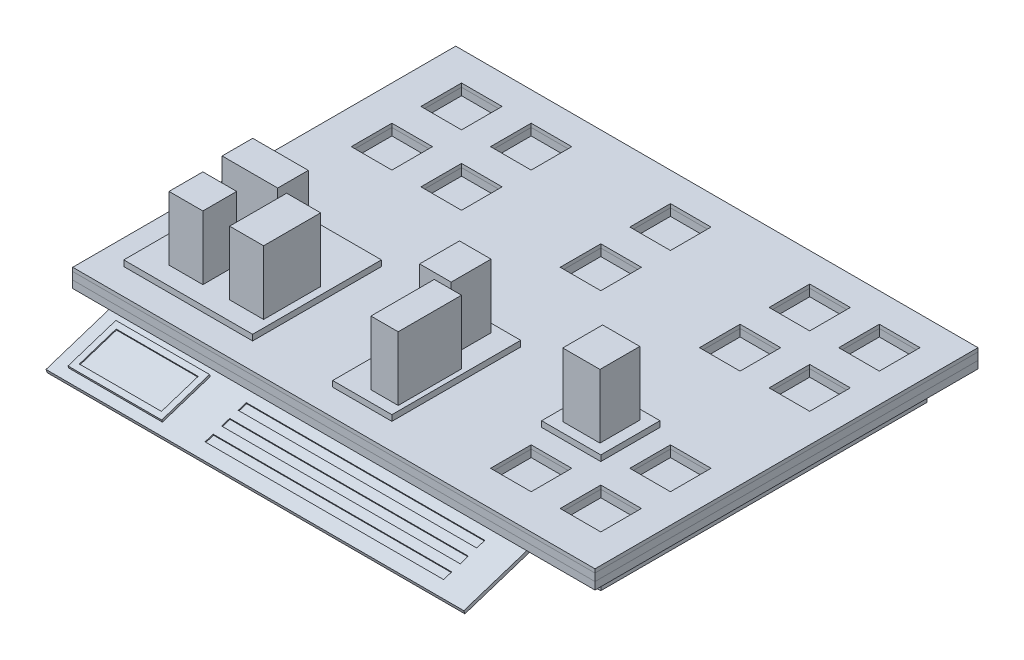
SolidWorks part; units mm, degrees
ref_plane "Front Plane" through (0, 0, 0) normal (0, 0, 1) x (1, 0, 0)
ref_plane "Top Plane" through (0, 0, 0) normal (0, 1, 0) x (1, 0, 0)
ref_plane "Right Plane" through (0, 0, 0) normal (1, 0, 0) x (0, 0, -1)
sketch "Sketch2" plane through (0, 0, 0) normal (0, 1, 0) x (1, 0, 0)
  line L0 (60, 0) -> (60, 35)
  line L1 (0, 0) -> (35, 0)
  line L2 (0, 0) -> (0, 35)
  line L3 (0, 35) -> (35, 35)
  line L4 (35, 0) -> (35, 35)
  line L5 (-30, -30) -> (420, -30)
  line L6 (-30, -30) -> (-30, 300)
  line L7 (-30, 300) -> (420, 300)
  line L8 (420, -30) -> (420, 300)
  line L9 (60, 0) -> (95, 0)
  line L10 (95, 0) -> (95, 35)
  line L11 (60, 35) -> (95, 35)
  line L12 (120, 0) -> (120, 35)
  line L13 (120, 0) -> (155, 0)
  line L14 (155, 0) -> (155, 35)
  line L15 (120, 35) -> (155, 35)
  line L16 (180, 0) -> (180, 35)
  line L17 (180, 0) -> (215, 0)
  line L18 (215, 0) -> (215, 35)
  line L19 (180, 35) -> (215, 35)
  line L20 (240, 0) -> (240, 35)
  line L21 (240, 0) -> (275, 0)
  line L22 (275, 0) -> (275, 35)
  line L23 (240, 35) -> (275, 35)
  line L24 (300, 0) -> (300, 35)
  line L25 (300, 0) -> (335, 0)
  line L26 (335, 0) -> (335, 35)
  line L27 (300, 35) -> (335, 35)
  line L28 (360, 0) -> (360, 35)
  line L29 (360, 0) -> (395, 0)
  line L30 (395, 0) -> (395, 35)
  line L31 (360, 35) -> (395, 35)
  line L32 (60, 60) -> (60, 95)
  line L33 (60, 60) -> (95, 60)
  line L34 (95, 60) -> (95, 95)
  line L35 (60, 95) -> (95, 95)
  line L36 (120, 60) -> (120, 95)
  line L37 (120, 60) -> (155, 60)
  line L38 (155, 60) -> (155, 95)
  line L39 (120, 95) -> (155, 95)
  line L40 (180, 60) -> (180, 95)
  line L41 (180, 60) -> (215, 60)
  line L42 (215, 60) -> (215, 95)
  line L43 (180, 95) -> (215, 95)
  line L44 (240, 60) -> (240, 95)
  line L45 (240, 60) -> (275, 60)
  line L46 (275, 60) -> (275, 95)
  line L47 (240, 95) -> (275, 95)
  line L48 (300, 60) -> (300, 95)
  line L49 (300, 60) -> (335, 60)
  line L50 (335, 60) -> (335, 95)
  line L51 (300, 95) -> (335, 95)
  line L52 (360, 60) -> (360, 95)
  line L53 (360, 60) -> (395, 60)
  line L54 (395, 60) -> (395, 95)
  line L55 (360, 95) -> (395, 95)
  line L56 (60, 120) -> (60, 155)
  line L57 (60, 120) -> (95, 120)
  line L58 (95, 120) -> (95, 155)
  line L59 (60, 155) -> (95, 155)
  line L60 (120, 120) -> (120, 155)
  line L61 (120, 120) -> (155, 120)
  line L62 (155, 120) -> (155, 155)
  line L63 (120, 155) -> (155, 155)
  line L64 (180, 120) -> (180, 155)
  line L65 (180, 120) -> (215, 120)
  line L66 (215, 120) -> (215, 155)
  line L67 (180, 155) -> (215, 155)
  line L68 (240, 120) -> (240, 155)
  line L69 (240, 120) -> (275, 120)
  line L70 (275, 120) -> (275, 155)
  line L71 (240, 155) -> (275, 155)
  line L72 (300, 120) -> (300, 155)
  line L73 (300, 120) -> (335, 120)
  line L74 (335, 120) -> (335, 155)
  line L75 (300, 155) -> (335, 155)
  line L76 (360, 120) -> (360, 155)
  line L77 (360, 120) -> (395, 120)
  line L78 (395, 120) -> (395, 155)
  line L79 (360, 155) -> (395, 155)
  line L80 (60, 180) -> (60, 215)
  line L81 (60, 180) -> (95, 180)
  line L82 (95, 180) -> (95, 215)
  line L83 (60, 215) -> (95, 215)
  line L84 (120, 180) -> (120, 215)
  line L85 (120, 180) -> (155, 180)
  line L86 (155, 180) -> (155, 215)
  line L87 (120, 215) -> (155, 215)
  line L88 (180, 180) -> (180, 215)
  line L89 (180, 180) -> (215, 180)
  line L90 (215, 180) -> (215, 215)
  line L91 (180, 215) -> (215, 215)
  line L92 (240, 180) -> (240, 215)
  line L93 (240, 180) -> (275, 180)
  line L94 (275, 180) -> (275, 215)
  line L95 (240, 215) -> (275, 215)
  line L96 (300, 180) -> (300, 215)
  line L97 (300, 180) -> (335, 180)
  line L98 (335, 180) -> (335, 215)
  line L99 (300, 215) -> (335, 215)
  line L100 (360, 180) -> (360, 215)
  line L101 (360, 180) -> (395, 180)
  line L102 (395, 180) -> (395, 215)
  line L103 (360, 215) -> (395, 215)
  line L104 (60, 240) -> (60, 275)
  line L105 (60, 240) -> (95, 240)
  line L106 (95, 240) -> (95, 275)
  line L107 (60, 275) -> (95, 275)
  line L108 (120, 240) -> (120, 275)
  line L109 (120, 240) -> (155, 240)
  line L110 (155, 240) -> (155, 275)
  line L111 (120, 275) -> (155, 275)
  line L112 (180, 240) -> (180, 275)
  line L113 (180, 240) -> (215, 240)
  line L114 (215, 240) -> (215, 275)
  line L115 (180, 275) -> (215, 275)
  line L116 (240, 240) -> (240, 275)
  line L117 (240, 240) -> (275, 240)
  line L118 (275, 240) -> (275, 275)
  line L119 (240, 275) -> (275, 275)
  line L120 (300, 240) -> (300, 275)
  line L121 (300, 240) -> (335, 240)
  line L122 (335, 240) -> (335, 275)
  line L123 (300, 275) -> (335, 275)
  line L124 (360, 240) -> (360, 275)
  line L125 (360, 240) -> (395, 240)
  line L126 (395, 240) -> (395, 275)
  line L127 (360, 275) -> (395, 275)
  line L128 (0, 60) -> (0, 95)
  line L129 (0, 60) -> (35, 60)
  line L130 (35, 60) -> (35, 95)
  line L131 (0, 95) -> (35, 95)
  line L132 (0, 120) -> (0, 155)
  line L133 (0, 120) -> (35, 120)
  line L134 (35, 120) -> (35, 155)
  line L135 (0, 155) -> (35, 155)
  line L136 (0, 180) -> (0, 215)
  line L137 (0, 180) -> (35, 180)
  line L138 (35, 180) -> (35, 215)
  line L139 (0, 215) -> (35, 215)
  line L140 (0, 240) -> (0, 275)
  line L141 (0, 240) -> (35, 240)
  line L142 (35, 240) -> (35, 275)
  line L143 (0, 275) -> (35, 275)
  dimension "D1" = 35
  dimension "D2" = 30
  dimension "D3" = 30
  dimension "D6" = 25
  dimension "D7" = 25
  dimension "D8" = 25
  dimension "D9" = 25
  dimension "D4" = 7
  dimension "D5" = 5
extrude "Boss-Extrude1" add sketch "Sketch2" along normal blind 6.35 contours L5 L8 L7 L6 | L4 L3 L2 L1 | L130 L131 L128 L129 | L34 L35 L32 L33 | L10 L11 L0 L9 | L138 L139 L136 L137 | L142 L143 L140 L141 | L104 L107 L106 L105 | L80 L83 L82 L81 | L112 L115 L114 L113 | L90 L91 L88 L89 | L120 L123 L122 L121 | L96 L99 L98 L97 | L124 L127 L126 L125 | L100 L103 L102 L101 | L52 L55 L54 L53 | L28 L31 L30 L29 | L50 L51 L48 L49 | L24 L27 L26 L25 | L18 L19 L16 L17 | L42 L43 L40 L41
extrude "Boss-Extrude11" add sketch "Sketch2<4>" along normal blind 3.175 from surface separate body contours L5 L8 L7 L6 L4 L1 L2 L3 L0 L11 L10 L9 L12 L15 L14 L13 L16 L19 L18 L17 L20 L23 L22 L21 L24 L27 L26 L25 L28 L31 L30 L29 L32 L35 L34 L33 L36 L39 L38 L37 L40 | L135 L132 L133 L134 | L59 L56 L57 L58 | L63 L60 L61 L62 | L87 L84 L85 L86 | L111 L108 L109 L110 | L67 L64 L65 L66 | L39 L36 L37 L38 | L15 L12 L13 L14 | L23 L20 L21 L22 | L47 L44 L45 L46 | L71 L68 L69 L70 | L95 L92 L93 L94 | L119 L116 L117 L118 | L75 L72 L73 L74 | L79 L76 L77 L78 region at (-24.4197, 0, -135) region at (137.5, 0, -17.5) region at (257.5, 0, -17.5) region at (137.5, 0, -77.5) region at (257.5, 0, -77.5) region at (77.5, 0, -137.5) region at (137.5, 0, -137.5) region at (197.5, 0, -137.5) region at (257.5, 0, -137.5) region at (317.5, 0, -137.5) region at (377.5, 0, -137.5) region at (137.5, 0, -197.5) region at (257.5, 0, -197.5) region at (137.5, 0, -257.5) region at (257.5, 0, -257.5) region at (17.5, 0, -137.5) starting at face at (197.5, 6.35, -17.5)
sketch "Sketch2<4>" plane through (0, 0, 0) normal (0, 1, 0) x (1, 0, 0) same geometry as "Sketch2"
extrude "Boss-Extrude2" add sketch "Sketch2<3>" against normal blind 6.35 separate body contours L6 L7 L8 L5
sketch "Sketch2<3>" plane through (0, 0, 0) normal (0, 1, 0) x (1, 0, 0) same geometry as "Sketch2"
sketch "Sketch3" plane through (0, -6.35, 0) normal (0, -1, 0) x (1, 0, 0)
  line L0 (420, 30) -> (420, -300) construction
  line L1 (0, 0) -> (395, 0)
  line L2 (0, 0) -> (0, -275)
  line L3 (0, -275) -> (395, -275)
  line L4 (395, 0) -> (395, -275)
  line L5 (-30, -300) -> (420, -300) construction
  dimension "D1" = 25
  dimension "D2" = 25
extrude "Extrude-Thin1" add sketch "Sketch3" along normal blind 25 separate body thin thin type one direction wall 3
ref_plane "Plane1" through (0, -4.862, -1.5797) normal (0, 0.9511, 0.309) x (-1, 0, 0)
sketch "Sketch4" plane through (0, -6.9572, 4.8686) normal (0, 0.9511, 0.309) x (1, 0, 0)
  line L0 (123.1064, -51.5258) -> (123.1064, -44.2135)
  line L1 (-3, -78.0352) -> (357, -78.0352)
  line L2 (-3, -78.0352) -> (-3, 1.9648)
  line L3 (-3, 1.9648) -> (357, 1.9648)
  line L4 (357, -78.0352) -> (357, 1.9648)
  line L5 (123.1064, -66.5258) -> (328.6551, -66.5258)
  line L6 (123.1064, -66.5258) -> (123.1064, -59.2135)
  line L7 (123.1064, -59.2135) -> (328.6551, -59.2135)
  line L8 (328.6551, -66.5258) -> (328.6551, -59.2135)
  line L9 (123.1064, -51.5258) -> (328.6551, -51.5258)
  line L10 (328.6551, -51.5258) -> (328.6551, -44.2135)
  line L11 (123.1064, -44.2135) -> (328.6551, -44.2135)
  line L12 (123.1064, -36.5258) -> (123.1064, -29.2135)
  line L13 (123.1064, -36.5258) -> (328.6551, -36.5258)
  line L14 (328.6551, -36.5258) -> (328.6551, -29.2135)
  line L15 (123.1064, -29.2135) -> (328.6551, -29.2135)
  line L16 (398, 1.9648) -> (-3, 1.9648) construction
  line L17 (11.4403, -66.4419) -> (86.1342, -66.4419)
  line L18 (11.4403, -66.4419) -> (11.4403, -29.1295)
  line L19 (11.4403, -29.1295) -> (86.1342, -29.1295)
  line L20 (86.1342, -66.4419) -> (86.1342, -29.1295)
  dimension "D2" = 360
  dimension "D3" = 80
  dimension "D1" = 3
extrude "Boss-Extrude3" add sketch "Sketch4" along normal blind 3 separate body
sketch "Sketch7" plane through (0, 6.35, 0) normal (0, 1, 0) x (1, 0, 0)
  line L0 (-30, 165) -> (110, 165)
  line L1 (-30, -30) -> (-30, 300) construction
  line L2 (420, -30) -> (420, 300) construction
  line L3 (-30, 110) -> (110, 110)
  line L4 (110, 300) -> (110, 165)
  line L5 (-30, 300) -> (420, 300) construction
  line L6 (-30, -30) -> (420, -30) construction
  line L7 (165, 300) -> (165, 165)
  line L8 (230, 300) -> (230, 165)
  line L9 (285, 300) -> (285, 165)
  line L10 (-30, 135) -> (420, 135) construction
  line L11 (142.5, 300) -> (142.5, -30) construction
  line L12 (262.5, 300) -> (262.5, -30) construction
  line L13 (0, 180) -> (35, 180) construction
  line L14 (0, 95) -> (35, 95) construction
  line L15 (95, 240) -> (95, 275) construction
  line L16 (180, 240) -> (180, 275) construction
  line L17 (215, 240) -> (215, 275) construction
  line L18 (300, 240) -> (300, 275) construction
  line L19 (110, 110) -> (110, -30)
  line L20 (165, 165) -> (230, 165)
  line L21 (165, 110) -> (230, 110)
  line L22 (165, 110) -> (165, -30)
  line L23 (230, 110) -> (230, -30)
  line L24 (285, 165) -> (420, 165)
  line L25 (285, 110) -> (285, -30)
  line L26 (285, 110) -> (420, 110)
  point P32 (95, 257.5)
  dimension "D1" = 15
  dimension "D2" = 15
  dimension "D3" = 15
  dimension "D4" = 15
  dimension "D5" = 15
  dimension "D6" = 15
  dimension "D7" = 32.5
  dimension "D8" = 32.5
sketch "Sketch5" plane through (0, 6.35, 0) normal (0, 1, 0) x (1, 0, 0)
  line L0 (0, 60) -> (0, 95) construction
  line L1 (-8, 103) -> (103, 103)
  line L2 (-8, 103) -> (-8, -8)
  line L3 (-8, -8) -> (103, -8)
  line L4 (103, 103) -> (103, -8)
  line L5 (0, 95) -> (35, 95) construction
  line L6 (95, 60) -> (95, 95) construction
  line L7 (60, 0) -> (95, 0) construction
  line L16 (1, 61) -> (34, 61)
  line L17 (1, 94) -> (1, 61)
  line L18 (34, 94) -> (1, 94)
  line L19 (34, 61) -> (34, 94)
  line L20 (1, 61) -> (34, 61)
  line L21 (1, 94) -> (1, 61)
  line L22 (34, 94) -> (1, 94)
  line L23 (34, 61) -> (34, 94)
  line L28 (94, 61) -> (94, 94)
  line L29 (94, 94) -> (61, 94)
  line L30 (61, 94) -> (61, 61)
  line L31 (61, 61) -> (94, 61)
  line L32 (94, 61) -> (94, 94)
  line L33 (94, 94) -> (61, 94)
  line L34 (61, 94) -> (61, 61)
  line L35 (61, 61) -> (94, 61)
  line L36 (181, 1) -> (214, 1)
  line L37 (181, 34) -> (181, 1)
  line L38 (214, 34) -> (181, 34)
  line L39 (214, 1) -> (214, 34)
  line L40 (181, 1) -> (214, 1)
  line L41 (1, 1) -> (34, 1)
  line L42 (1, 34) -> (1, 1)
  line L43 (34, 34) -> (1, 34)
  line L44 (34, 1) -> (34, 34)
  line L45 (1, 1) -> (34, 1)
  line L46 (1, 34) -> (1, 1)
  line L47 (34, 34) -> (1, 34)
  line L48 (34, 1) -> (34, 34)
  line L49 (180, 60) -> (180, 95) construction
  line L50 (172, 103) -> (223, 103)
  line L51 (172, 103) -> (172, -8)
  line L52 (172, -8) -> (223, -8)
  line L53 (61, 1) -> (94, 1)
  line L54 (94, 1) -> (94, 34)
  line L55 (94, 34) -> (61, 34)
  line L56 (61, 34) -> (61, 1)
  line L57 (61, 1) -> (94, 1)
  line L58 (94, 1) -> (94, 34)
  line L59 (94, 34) -> (61, 34)
  line L60 (61, 34) -> (61, 1)
  line L61 (223, 103) -> (223, -8)
  line L62 (215, 60) -> (215, 95) construction
  line L63 (181, 34) -> (181, 1)
  line L64 (214, 34) -> (181, 34)
  line L65 (214, 1) -> (214, 34)
  line L71 (214, 61) -> (214, 94)
  line L72 (214, 94) -> (181, 94)
  line L73 (181, 94) -> (181, 61)
  line L74 (181, 61) -> (214, 61)
  line L75 (214, 61) -> (214, 94)
  line L76 (214, 94) -> (181, 94)
  line L77 (181, 94) -> (181, 61)
  line L78 (181, 61) -> (214, 61)
  line L83 (300, 60) -> (300, 95) construction
  line L84 (292, 103) -> (343, 103)
  line L85 (292, 103) -> (292, 52)
  line L86 (292, 52) -> (343, 52)
  line L87 (343, 103) -> (343, 52)
  line L88 (300, 95) -> (335, 95) construction
  line L89 (300, 60) -> (335, 60) construction
  line L90 (335, 60) -> (335, 95) construction
  line L99 (301, 61) -> (334, 61)
  line L100 (301, 94) -> (301, 61)
  line L101 (334, 94) -> (301, 94)
  line L102 (334, 61) -> (334, 94)
  line L103 (301, 61) -> (334, 61)
  line L104 (301, 94) -> (301, 61)
  line L105 (334, 94) -> (301, 94)
  line L106 (334, 61) -> (334, 94)
  dimension "D1" = 8
  dimension "D2" = 8
  dimension "D3" = 8
  dimension "D4" = 8
  dimension "D9" = 8
  dimension "D10" = 8
  dimension "D12" = 8
  dimension "D13" = 8
  dimension "D14" = 8
  dimension "D15" = 8
  dimension "D5" = 1
  dimension "D6" = 1
  dimension "D7" = 1
  dimension "D8" = 1
  dimension "D11" = 1
  dimension "D16" = 1
  dimension "D17" = 1
extrude "Boss-Extrude4" add sketch "Sketch5" along normal offset from surface (3.675 mm away) 0.5 separate body contours L20 L23 L22 L21 | L34 L35 L32 L33 | L59 L60 L57 L58 | L45 L48 L47 L46 | L77 L78 L75 L76 | L103 L106 L105 L104 region at (17.5, 6.35, -77.5) region at (77.5, 6.35, -77.5) region at (17.5, 6.35, -17.5) region at (77.5, 6.35, -17.5) region at (197.5, 6.35, -77.5) region at (317.5, 6.35, -77.5) up to face at (17.5, 9.525, -17.5) offset beyond the face yes
extrude "Boss-Extrude5" add sketch "Sketch5<3>" along normal blind 5 from surface contours L1 L4 L3 L2 | L50 L61 L52 L51 | L84 L87 L86 L85 starting at face at (17.5, 10.025, -77.5)
sketch "Sketch5<3>" plane through (0, 6.35, 0) normal (0, 1, 0) x (1, 0, 0) same geometry as "Sketch5"
sketch "Sketch6" plane through (0, 15.025, 0) normal (0, 1, 0) x (1, 0, 0)
  line L1 (15.3942, 36.744) -> (44.5535, 36.744)
  line L2 (15.3942, 36.744) -> (15.3942, 7.5846)
  line L3 (15.3942, 7.5846) -> (44.5535, 7.5846)
  line L4 (44.5535, 36.744) -> (44.5535, 7.5846)
  line L5 (11.805, 83.2867) -> (59.6939, 83.2867)
  line L6 (11.805, 83.2867) -> (11.805, 56.9312)
  line L7 (11.805, 56.9312) -> (59.6939, 56.9312)
  line L8 (59.6939, 83.2867) -> (59.6939, 56.9312)
  line L9 (67.4253, 7.7676) -> (96.7038, 7.7676)
  line L10 (67.4253, 7.7676) -> (67.4253, 56.9312)
  line L11 (67.4253, 56.9312) -> (96.7038, 56.9312)
  line L12 (96.7038, 7.7676) -> (96.7038, 56.9312)
  line L13 (177.4469, 95.783) -> (204.639, 95.783)
  line L14 (177.4469, 95.783) -> (177.4469, 61.4629)
  line L15 (177.4469, 61.4629) -> (204.639, 61.4629)
  line L16 (204.639, 95.783) -> (204.639, 61.4629)
  line L17 (195.3587, 56.1581) -> (218.8547, 56.1581)
  line L18 (195.3587, 56.1581) -> (195.3587, 1.5747)
  line L19 (195.3587, 1.5747) -> (218.8547, 1.5747)
  line L20 (218.8547, 56.1581) -> (218.8547, 1.5747)
  line L21 (301.8162, 94.7332) -> (333.8719, 94.7332)
  line L22 (301.8162, 94.7332) -> (301.8162, 60.4131)
  line L23 (301.8162, 60.4131) -> (333.8719, 60.4131)
  line L24 (333.8719, 94.7332) -> (333.8719, 60.4131)
extrude "Boss-Extrude6" add sketch "Sketch6" along normal blind 55
sketch "Sketch8" plane through (0, -2.0088, -0.6527) normal (0, 0.9511, 0.309) x (1, 0, 0)
  line L4 (13.4403, -71.2221) -> (84.1342, -71.2221)
  line L5 (84.1342, -71.2221) -> (84.1342, -37.9097)
  line L6 (84.1342, -37.9097) -> (13.4403, -37.9097)
  line L7 (13.4403, -37.9097) -> (13.4403, -71.2221)
  line L8 (8.4403, -76.2221) -> (89.1342, -76.2221)
  line L9 (89.1342, -76.2221) -> (89.1342, -32.9097)
  line L10 (89.1342, -32.9097) -> (8.4403, -32.9097)
  line L11 (8.4403, -32.9097) -> (8.4403, -76.2221)
  line L12 (8.4403, -76.2221) -> (89.1342, -76.2221)
  line L13 (89.1342, -76.2221) -> (89.1342, -32.9097)
  line L14 (89.1342, -32.9097) -> (8.4403, -32.9097)
  line L15 (8.4403, -32.9097) -> (8.4403, -76.2221)
  dimension "D1" = 3
  dimension "D2" = 5
extrude "Boss-Extrude7" add sketch "Sketch8" along normal blind 1 separate body contours L6 L7 L4 L5 region at (48.7872, -18.8706, 51.2426)
extrude "Boss-Extrude8" add sketch "Sketch8<3>" along normal blind 2
sketch "Sketch8<3>" plane through (0, -2.0088, -0.6527) normal (0, 0.9511, 0.309) x (1, 0, 0) same geometry as "Sketch8"
extrude "Boss-Extrude9" add sketch "Sketch4<2>" along normal blind 2 contours L15 L12 L13 L14 | L11 L10 L9 L0 | L7 L8 L5 L6 region at (225.8808, -17.1144, 36.1295)
sketch "Sketch4<2>" plane through (0, -6.9572, 4.8686) normal (0, 0.9511, 0.309) x (1, 0, 0) same geometry as "Sketch4"
sketch "Sketch9" plane through (0, 0, 3) normal (0, 0, 1) x (1, 0, 0)
  line L0 (398, -6.35) -> (-3, -6.35) construction
  line L1 (14.2588, -6.35) -> (64.0119, -6.35)
  line L2 (14.2588, -6.35) -> (14.2588, -11.6704)
  line L3 (14.2588, -11.6704) -> (64.0119, -11.6704)
  line L4 (64.0119, -6.35) -> (64.0119, -11.6704)
extrude "Cut-Extrude1" cut sketch "Sketch9" against normal up to next (3 mm away)
sketch3d "3DSketch3" [suppressed]
  line L0 (162.1791, -23.9893, 57.2883) -> (25.2639, -23.9893, 57.2883)
  line L1 (162.1791, -18.1813, 39.4129) -> (31.5704, -18.1813, 39.4129)
  line L2 (162.1791, -14.1972, 27.1511) -> (42.2769, -14.1972, 27.1511)
  line L3 (42.2769, -14.1972, 27.1511) -> (38.8831, -6.35, 3)
  line L4 (357, -6.35, 3) -> (-3, -6.35, 3) construction
  line L5 (31.5704, -18.1813, 39.4129) -> (32.2727, -6.2255, 2.6168)
  line L6 (39.429, -6.35, -130.7165) -> (25.2639, -6.35, 3)
  line L7 (25.2639, -23.9893, 57.2883) -> (25.2639, -6.35, 3)
  line L8 (20.7749, -15.9587, 32.5725) -> (14.5755, -6.35, 3)
  line L9 (86.1342, -15.9587, 32.5725) -> (11.4403, -15.9587, 32.5725) construction
  line L10 (14.5755, -6.35, -294.7956) -> (14.5755, -6.35, 3)
  line L12 (14.5755, -6.35, -145.0538) -> (32.3401, -6.35, -145.0538)
  line L13 (32.3402, -6.35, -160.5463) -> (32.3401, -6.35, -130.7166)
  line L14 (32.3402, -6.35, -160.5463) -> (102.4682, -6.35, -160.5461)
  line L15 (102.4682, -6.35, -160.5461) -> (102.4681, -6.35, -130.7163)
  line L16 (32.3401, -6.35, -130.7166) -> (102.4681, -6.35, -130.7163)
  line L18 (47.4433, -6.35, -130.7165) -> (32.2727, -6.2255, 2.6168)
  line L19 (54.9504, -6.35, -130.7165) -> (38.8831, -6.35, 3)
sketch "Sketch10" plane through (0, 0, -278) normal (0, 0, -1) x (-1, 0, 0)
  circle A0 centre (-15.9636, -11.6907) radius 2.5
  dimension "D1" = 5
move or copy body "Body-Move/Copy1" [suppressed] bodies to move or copy 115 copy no translate (-298.1195, 0, 0) parameters "D1"=298.1195, "D2"=0, "D3"=0
move or copy body "Body-Move/Copy2" [suppressed] bodies to move or copy 116 copy no translate (-361.2244, 0, 0) parameters "D1"=361.2244, "D2"=0, "D3"=0
move or copy body "Body-Move/Copy3" [suppressed] bodies to move or copy 117 copy no translate (-427.7801, 0, 65.9497) parameters "D1"=427.7801, "D2"=0, "D3"=65.9497
move or copy body "Body-Move/Copy4" [suppressed] bodies to move or copy 120 119 copy no rotation origin (0, -13.9688, 41.6337) rotation axis (-1, 0, 0) rotation angle 21
move or copy body "Body-Move/Copy5" [suppressed] bodies to move or copy 132 133 copy no translate (0, 6.9158, 0) parameters "D1"=0, "D2"=6.9158, "D3"=0
equation "\"D6@Sketch5\"=\"D5@Sketch5\""
equation "\"D7@Sketch5\"=\"D5@Sketch5\""
equation "\"D8@Sketch5\"=\"D5@Sketch5\""
equation "\"D11@Sketch5\"=\"D5@Sketch5\""
equation "\"D17@Sketch5\"=\"D5@Sketch5\""
equation "\"D16@Sketch5\"=\"D5@Sketch5\""
